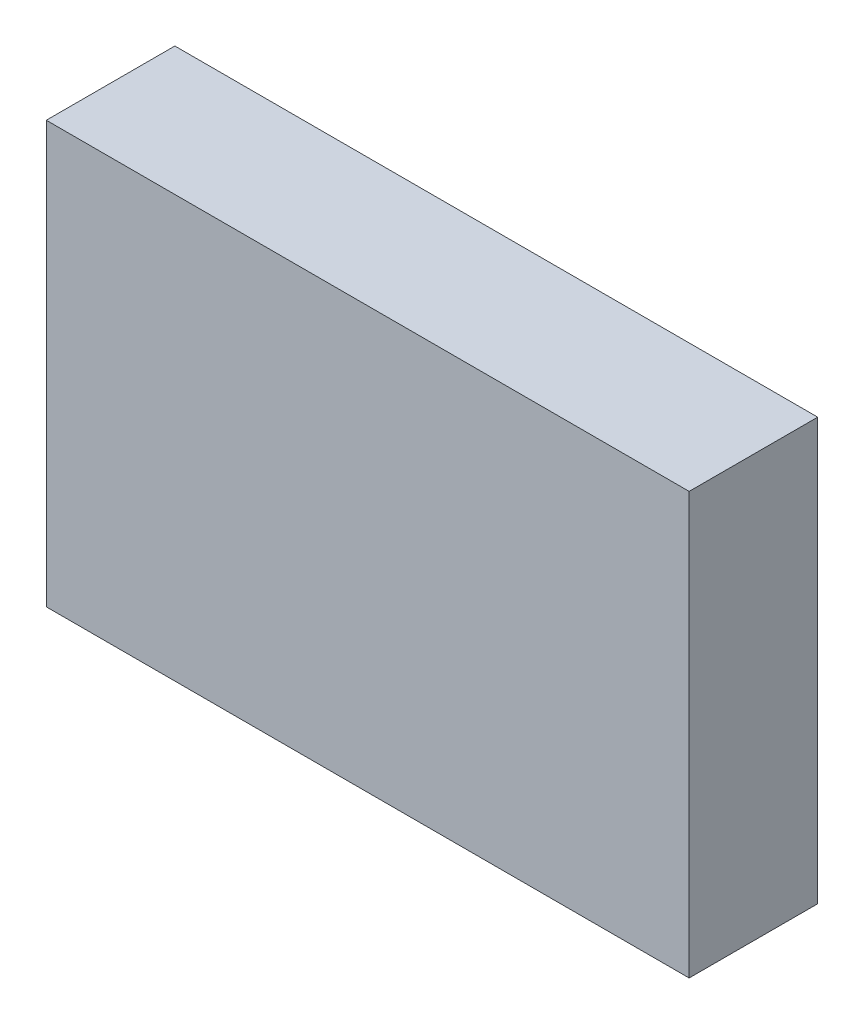
SolidWorks part; units mm, degrees
material "Plomb pur"
ref_plane "Front" through (0, 0, 0) normal (0, 0, 1) x (1, 0, 0)
ref_plane "Top" through (0, 0, 0) normal (0, 1, 0) x (1, 0, 0)
ref_plane "Right" through (0, 0, 0) normal (1, 0, 0) x (0, 0, -1)
sketch "Esquisse1" plane through (0, 0, 0) normal (0, 0, 1) x (1, 0, 0)
  line L1 (0, 0) -> (90, 0)
  line L2 (0, 0) -> (0, 59)
  line L3 (0, 59) -> (90, 59)
  line L4 (90, 0) -> (90, 59)
  dimension "D1" = 90
  dimension "D2" = 59
extrude "Boss.-Extru.1" add sketch "Esquisse1" along normal blind 18
